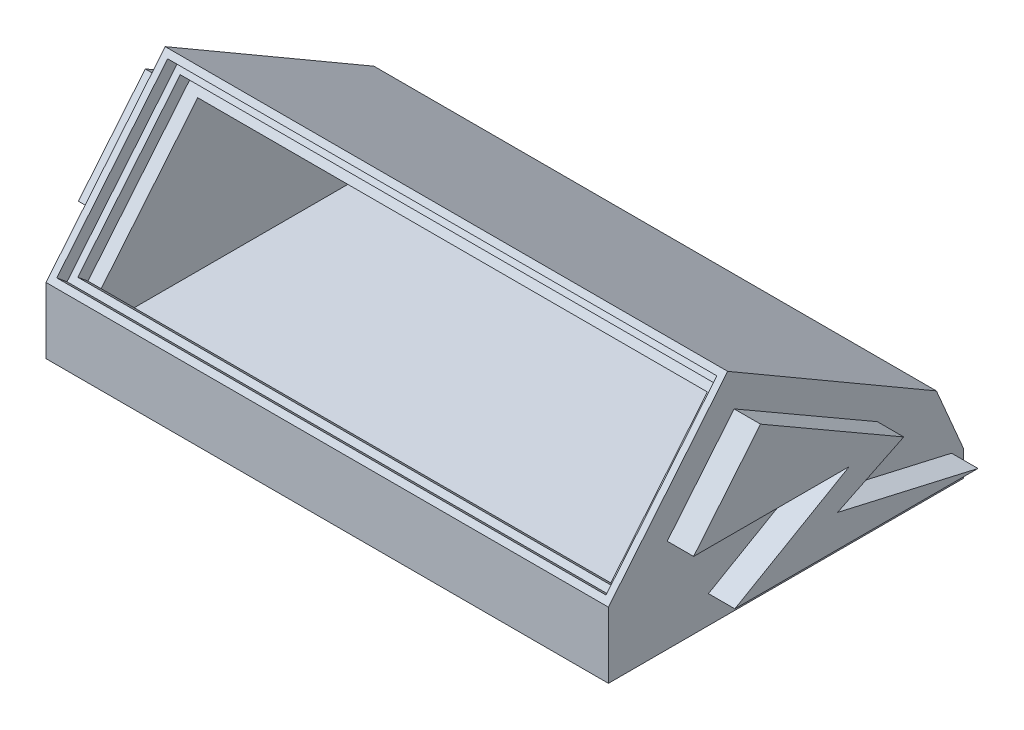
SolidWorks part; units mm, degrees
ref_plane "Front Plane" through (0, 0, 0) normal (0, 0, 1) x (1, 0, 0)
ref_plane "Top Plane" through (0, 0, 0) normal (0, 1, 0) x (1, 0, 0)
ref_plane "Right Plane" through (0, 0, 0) normal (1, 0, 0) x (0, 0, -1)
sketch "Sketch1" plane through (0, 0, 0) normal (1, 0, 0) x (0, 0, -1)
  line L3 (-49, -28) -> (49, -28)
  line L4 (49, -18) -> (49, -28)
  line L5 (-40.2362, 51.7571) -> (38.8138, 5.8207)
  line L8 (-40.2362, 51.7571) -> (-85.3941, -3)
  line L9 (-85.3941, -3) -> (-85.3941, -28)
  line L10 (-86.6954, -28) -> (82.3046, -28) construction
  line L11 (-85.3941, -28) -> (-49, -28)
  line L12 (38.8138, 5.8207) -> (49, -18)
  point P0 (0, 0)
extrude "Boss-Extrude1" add sketch "Sketch1" along normal mid plane 213
sketch "Sketch2" plane through (-106.5, 0, 0) normal (-1, 0, 0) x (0, 0, 1)
  line L4 (37.9064, 38.865) -> (-17.5189, 6.8652)
  line L5 (-17.5189, 6.8652) -> (7.1258, -5.1549)
  line L6 (7.1258, -5.1549) -> (-49, -18)
  line L7 (-49, -18) -> (49.3749, -18)
  line L8 (49.3749, -18) -> (6.0736, 7)
  line L9 (6.0736, 7) -> (64.1852, 7)
  line L10 (64.1852, 7) -> (37.9064, 38.865)
  line L11 (63.1248, 7.5) -> (37.7899, 38.2204)
  line L12 (37.7899, 38.2204) -> (-16.4546, 6.9023)
  line L13 (-16.4546, 6.9023) -> (8.6179, -5.3263)
  line L14 (8.6179, -5.3263) -> (-44.5741, -17.5)
  line L15 (-44.5741, -17.5) -> (47.5088, -17.5)
  line L16 (47.5088, -17.5) -> (4.2076, 7.5)
  line L17 (4.2076, 7.5) -> (63.1248, 7.5)
  dimension "D1" = 0.5
extrude "Boss-Extrude3" add sketch "Sketch2" along normal blind 10 contours L11 L12 L13 L14 L15 L16 L17
mirror "Mirror1" about plane through (0, 0, 0) normal (1, 0, 0) of "Boss-Extrude3"
sketch "Sketch3" plane through (0, 0, 0) normal (1, 0, 0) x (0, 0, -1)
  line L36 (38.1241, -18) -> (30.9228, -1.1596)
  line L37 (30.9228, -1.1596) -> (-37.9217, 38.8463)
  line L38 (-37.9217, 38.8463) -> (-75.3941, -6.5916)
  line L39 (-75.3941, -6.5916) -> (-75.3941, -18)
  line L40 (-75.3941, -18) -> (38.1241, -18)
  line L41 (38.1241, -18) -> (30.9228, -1.1596)
  line L42 (30.9228, -1.1596) -> (-37.9217, 38.8463)
  line L43 (-37.9217, 38.8463) -> (-75.3941, -6.5916)
  line L44 (-75.3941, -6.5916) -> (-75.3941, -18)
  line L45 (-75.3941, -18) -> (38.1241, -18)
  dimension "D1" = 10
extrude "Cut-Extrude1" cut sketch "Sketch3" against normal mid plane 193
sketch "Sketch7" plane through (0, 40.7016, 49.3536) normal (0, 0.6362, 0.7715) x (1, 0, 0)
  line L8 (-104, 11.8301) -> (-104, -54.1458)
  line L9 (-104, -54.1458) -> (104, -54.1458)
  line L10 (104, -54.1458) -> (104, 11.8301)
  line L11 (104, 11.8301) -> (-104, 11.8301)
  line L12 (-104, 11.8301) -> (-104, -54.1458)
  line L13 (-104, -54.1458) -> (104, -54.1458)
  line L14 (104, -54.1458) -> (104, 11.8301)
  line L15 (104, 11.8301) -> (-104, 11.8301)
  dimension "D1" = 2.5
extrude "Cut-Extrude4" cut sketch "Sketch7" against normal blind 5
sketch "Sketch8" plane through (0, 37.5204, 45.4962) normal (0, 0.6362, 0.7715) x (1, 0, 0)
  line L8 (101.5, 9.3301) -> (-101.5, 9.3301)
  line L9 (-101.5, 9.3301) -> (-101.5, -51.6458)
  line L10 (-101.5, -51.6458) -> (101.5, -51.6458)
  line L11 (101.5, -51.6458) -> (101.5, 9.3301)
  line L12 (101.5, 9.3301) -> (-101.5, 9.3301)
  line L13 (-101.5, 9.3301) -> (-101.5, -51.6458)
  line L14 (-101.5, -51.6458) -> (101.5, -51.6458)
  line L15 (101.5, -51.6458) -> (101.5, 9.3301)
  dimension "D1" = 2.5
extrude "Cut-Extrude5" cut sketch "Sketch8" against normal blind 5
